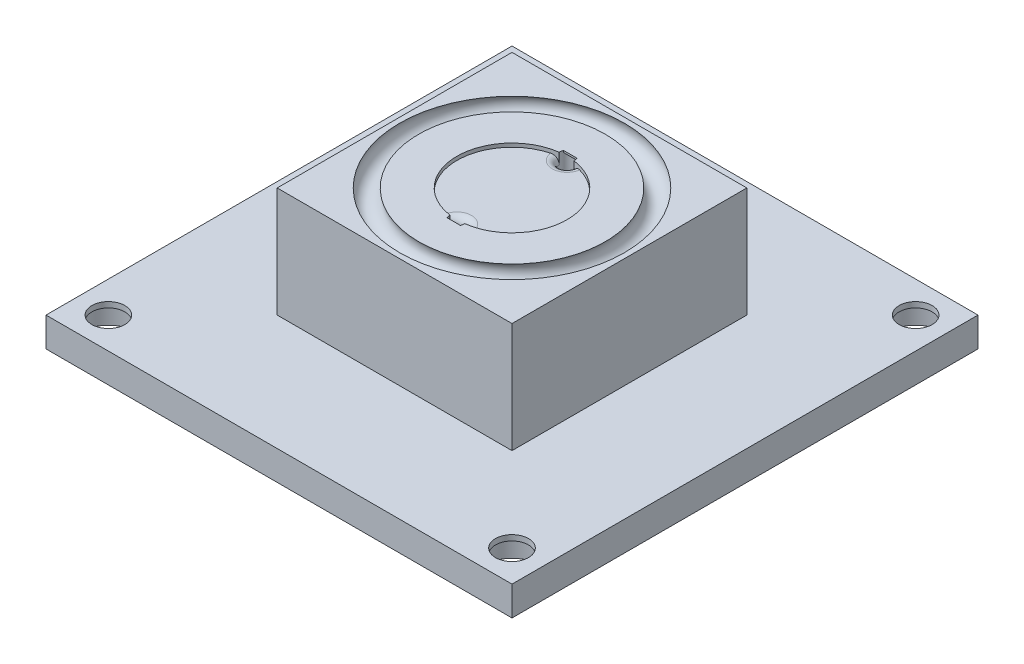
SolidWorks part; units mm, degrees
material "Custom Plastic"
ref_plane "Front Plane" through (0, 0, 0) normal (0, 0, 1) x (1, 0, 0)
ref_plane "Top Plane" through (0, 0, 0) normal (0, 1, 0) x (1, 0, 0)
ref_plane "Right Plane" through (0, 0, 0) normal (1, 0, 0) x (0, 0, -1)
sketch "Sketch1" plane through (0, 0, 0) normal (0, 1, 0) x (1, 0, 0)
  line L1 (-31.75, 31.75) -> (31.75, 31.75)
  line L2 (-31.75, 31.75) -> (-31.75, -31.75)
  line L3 (-31.75, -31.75) -> (31.75, -31.75)
  line L4 (31.75, 31.75) -> (31.75, -31.75)
  line L5 (-31.75, 31.75) -> (31.75, -31.75) construction
  line L6 (-31.75, -31.75) -> (31.75, 31.75) construction
  circle A2 centre (27.5, 27.5) radius 2.25
  circle A3 centre (27.5, -27.5) radius 2.25
  circle A4 centre (-27.5, -27.5) radius 2.25
  circle A5 centre (-27.5, 27.5) radius 2.25
extrude "main" add sketch "Sketch1" along normal blind 4
sketch "Sketch7" plane through (0, 0, 0) normal (0, 1, 0) x (1, 0, 0)
  circle A1 centre (0, 7.5) radius 1
  circle A2 centre (0, -7.5) radius 1
extrude "pipe1" add sketch "Sketch7" against normal blind 25 separate body
sketch "Sketch14" plane through (0, 0, 0) normal (1, 0, 0) x (0, 0, -1)
  circle A0 centre (14, -0.75) radius 1.5
  point P2 (0, 0)
  point P3 (0, 0)
sketch "Sketch50" plane through (0, 0, 0) normal (0, 0, 1) x (1, 0, 0)
  line L0 (0, 0) -> (0, 28.041) construction
revolve "Revolve1" add sketch "Sketch14" angle 360 about L0
sketch "Sketch52" plane through (0, 0, 0) normal (0, 1, 0) x (1, 0, 0)
  circle A2 centre (27.5, 27.5) radius 3.95
  circle A3 centre (27.5, -27.5) radius 3.95
  circle A4 centre (-27.5, -27.5) radius 3.95
  circle A5 centre (-27.5, 27.5) radius 3.95
extrude "Boss-Extrude11" add sketch "Sketch52" along normal blind 3.25 separate body
sketch "Sketch56" plane through (0, 0, 0) normal (0, 1, 0) x (1, 0, 0)
  line L1 (-16, -16) -> (16, -16)
  line L2 (-16, -16) -> (-16, 16)
  line L3 (-16, 16) -> (16, 16)
  line L4 (16, -16) -> (16, 16)
  line L5 (-16, -16) -> (16, 16) construction
  line L6 (-16, 16) -> (16, -16) construction
  point P0 (0, 0)
extrude "Boss-Extrude14" add sketch "Sketch56" against normal blind 15 separate body
combine bodies "Combine14" operation type subtract main body 101 bodies to subtract 119 120 121 122
move or copy body "Body-Move/Copy1" bodies to move or copy 137 copy no translate (0, -19, 0)
combine bodies "Combine16" operation type add bodies to combine 138 135
sketch "Sketch57" plane through (0, 0, 0) normal (0, 1, 0) x (1, 0, 0)
  circle A0 centre (0, 0) radius 14
sketch "Sketch60" plane through (0, 0, 0) normal (0, 1, 0) x (1, 0, 0)
  circle A0 centre (0, 0) radius 14
  circle A1 centre (0, 0) radius 1
sketch "Sketch61" plane through (0, 0, 0) normal (0, 1, 0) x (1, 0, 0)
  circle A0 centre (0, 0) radius 7.5
  point P8 (0, 0)
extrude "Boss-Extrude16" add sketch "Sketch61" against normal blind 0.5 separate body
sketch "Sketch62" plane through (0, 0, 0) normal (0, 1, 0) x (1, 0, 0)
  line L0 (0, 7.5) -> (0, -7.5) construction
  line L1 (1, 7.5) -> (1, -7.5)
  line L2 (-1, 7.5) -> (-1, -7.5)
  arc A0 (1, 7.5) -> (-1, 7.5) centre (0, 7.5) ccw
  arc A1 (-1, -7.5) -> (1, -7.5) centre (0, -7.5) ccw
  point P4 (0, 0)
extrude "Boss-Extrude17" add sketch "Sketch62" against normal blind 0.5 separate body
ref_plane "Plane1" through (0, -19, 0) normal (0, -1, 0) x (-1, 0, 0)
sketch "Sketch63" plane through (0, -19, 0) normal (0, -1, 0) x (-1, 0, 0)
  circle A0 centre (0, 7.5) radius 1.75
  circle A1 centre (0, 7.5) radius 1
  circle A2 centre (0, -7.5) radius 1.75
  circle A3 centre (0, -7.5) radius 1
sketch "Sketch64" plane through (0, -19, 0) normal (0, -1, 0) x (-1, 0, 0)
  circle A0 centre (0, 0) radius 14
  circle A1 centre (0, 0) radius 1
combine bodies "Combine17" operation type subtract main body 139 bodies to subtract 114 157 158
extrude "Boss-Extrude18" add sketch "Sketch63" along normal blind 5 separate body
combine bodies "Combine18" operation type subtract main body 159 bodies to subtract 156 109
combine bodies "Combine19" operation type add bodies to combine 161 160 162
fillet "Fillet1" radius 2 2 edges at (0, -19, 5.75) (0, -19, -5.75)
ref_plane "Plane2" through (0, -24, 0) normal (0, -1, 0) x (-1, 0, 0)
sketch "Sketch65" plane through (0, -24, 0) normal (0, -1, 0) x (-1, 0, 0)
  circle A0 centre (0, 7.5) radius 2.25
  circle A1 centre (0, 7.5) radius 1
  circle A2 centre (0, -7.5) radius 2.25
  circle A3 centre (0, -7.5) radius 1
extrude "Boss-Extrude19" add sketch "Sketch65" along normal blind 3
chamfer "Chamfer1" distance 3 distance2 1 2 edges at (0, -27, 5.25) (0, -27, -9.75)
sketch "Sketch66" plane through (0, 0, 0) normal (0, 1, 0) x (1, 0, 0)
  circle A0 centre (0, 7.5) radius 2.25
  circle A1 centre (0, 7.5) radius 1
  circle A2 centre (0, -7.5) radius 2.25
extrude "Boss-Extrude20" add sketch "Sketch66" against normal blind 12 from offset 3 separate body offset against normal yes
combine bodies "Combine20" operation type subtract main body 164 bodies to subtract 166 167
sketch "Sketch67" plane through (0, 0, 0) normal (0, 1, 0) x (1, 0, 0)
  line L1 (1.5432, 7.9398) -> (-1.5432, 7.9398)
  line L2 (1.5432, 7.9398) -> (1.5432, 8.5602)
  line L3 (1.5432, 8.5602) -> (-1.5432, 8.5602)
  line L4 (-1.5432, 7.9398) -> (-1.5432, 8.5602)
  line L5 (1.5432, 7.9398) -> (-1.5432, 8.5602) construction
  line L6 (1.5432, 8.5602) -> (-1.5432, 7.9398) construction
  line L12 (1.5432, -8.5602) -> (-1.5432, -8.5602)
  line L13 (1.5432, -8.5602) -> (1.5432, -7.9398)
  line L14 (1.5432, -7.9398) -> (-1.5432, -7.9398)
  line L15 (-1.5432, -8.5602) -> (-1.5432, -7.9398)
  line L16 (1.5432, -8.5602) -> (-1.5432, -7.9398) construction
  line L17 (1.5432, -7.9398) -> (-1.5432, -8.5602) construction
  point P0 (0, 8.25)
  point P15 (0, -8.25)
extrude "Boss-Extrude21" add sketch "Sketch67" against normal blind 0.75
chamfer "Chamfer2" distance 0.5 angle 45 2 edges at (0, -0.75, -7.9398) (0, -0.75, 7.9398)
fillet "Fillet2" radius 1 6 edges at (0, -0.5, 6.5) (1, -0.5, 7.4665) (1, -0.5, -7.4665) (-1, -0.5, -7.4665) (-1, -0.5, 7.4665) (0, -0.5, -6.5)
